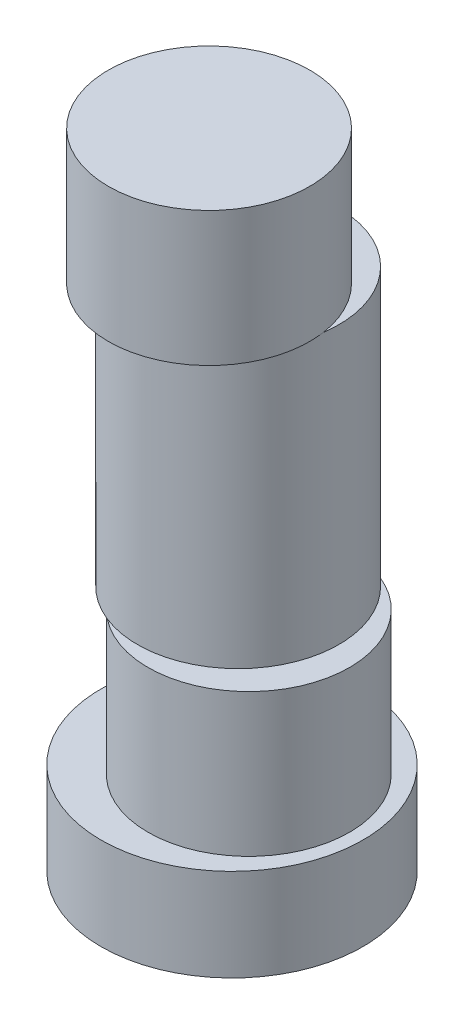
SolidWorks part; units mm, degrees
ref_plane "Front Plane" through (0, 0, 0) normal (0, 0, 1) x (1, 0, 0)
ref_plane "Top Plane" through (0, 0, 0) normal (0, 1, 0) x (1, 0, 0)
ref_plane "Right Plane" through (0, 0, 0) normal (1, 0, 0) x (0, 0, -1)
sketch "Sketch1" plane through (0, 0, 0) normal (0, 1, 0) x (1, 0, 0)
  circle A0 centre (0, 0) radius 7.8
  dimension "D1" = 15.6
extrude "Boss-Extrude1" add sketch "Sketch1" along normal blind 5.5
sketch "Sketch2" plane through (0, 5.5, 0) normal (0, 1, 0) x (1, 0, 0)
  line L0 (0, 0) -> (1, 0) construction
  circle A0 centre (1, 0) radius 6
  dimension "D2" = 12
extrude "Boss-Extrude2" add sketch "Sketch2" along normal blind 8.5
sketch "Sketch4" plane through (0, 14, 0) normal (0, 1, 0) x (1, 0, 0)
  line L0 (0, 0) -> (1, 0) construction
  line L1 (0, 0) -> (-0.5, 0.866) construction
  circle A0 centre (-0.5, 0.866) radius 6
  dimension "D4" = 12
  dimension "D1" = 120
  dimension "D2" = 1
  dimension "D3" = 1
extrude "Boss-Extrude3" add sketch "Sketch4" along normal blind 16.5
sketch "Sketch3" plane through (0, 0, 0) normal (0, -1, 0) x (1, 0, 0)
  circle A0 centre (0, 0) radius 3
  dimension "D1" = 6
extrude "Cut-Extrude2" cut sketch "Sketch3" against normal through all
sketch "Sketch7" plane through (0, 30.5, 0) normal (0, 1, 0) x (1, 0, 0)
  line L0 (0, 0) -> (-0.5, 0.866) construction
  line L1 (0, 0) -> (0, 1) construction
  line L2 (0, 0) -> (-0.5, -0.866) construction
  circle A0 centre (-0.5, -0.866) radius 6
  dimension "D6" = 12
  dimension "D1" = 1
  dimension "D2" = 1
  dimension "D3" = 30
  dimension "D4" = 120
  dimension "D5" = 1
extrude "Boss-Extrude4" add sketch "Sketch7" along normal blind 8
